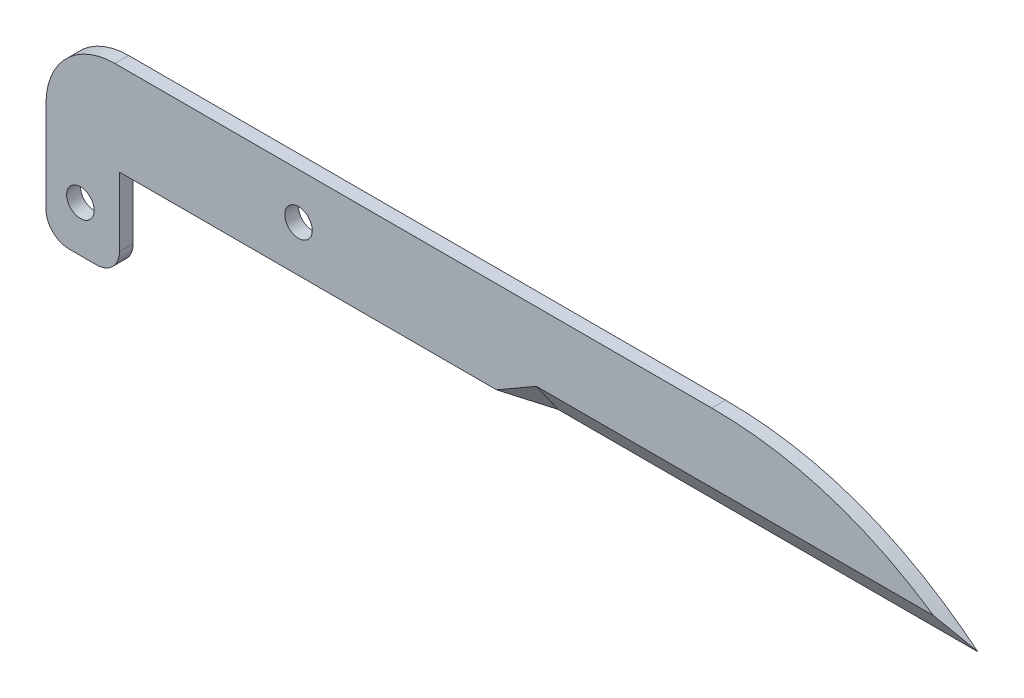
SolidWorks part; units mm, degrees
ref_plane "前视基准面" through (0, 0, 0) normal (0, 0, 1) x (1, 0, 0)
ref_plane "上视基准面" through (0, 0, 0) normal (0, 1, 0) x (1, 0, 0)
ref_plane "右视基准面" through (0, 0, 0) normal (1, 0, 0) x (0, 0, -1)
sketch "草图1" plane through (0, 0, 0) normal (0, 0, 1) x (1, 0, 0)
  line L1 (100, -10) -> (-100, -10)
  line L2 (100, -10) -> (100, 10)
  line L3 (100, 10) -> (-100, 10)
  line L4 (-100, -10) -> (-100, 10)
  line L5 (100, -10) -> (-100, 10) construction
  line L6 (100, 10) -> (-100, -10) construction
  point P0 (0, 0)
  dimension "D1" = 200
  dimension "D2" = 20
extrude "凸台-拉伸1" add sketch "草图1" along normal blind 3
sketch "草图2" plane through (0, 0, 3) normal (0, 0, 1) x (1, 0, 0)
  line L0 (21.8012, -4.3413) -> (12, -10) construction
  line L1 (-100, -10) -> (100, -10) construction
  dimension "D1" = 12
  dimension "D2" = 30
ref_plane "基准面1" through (7.3301, -12.6962, 0) normal (-0.5, 0.866, 0) x (-0.866, -0.5, 0)
sketch "草图3" plane through (100, 0, 0) normal (1, 0, 0) x (0, 0, -1)
  line L0 (-3, -5) -> (0, -10)
  line L1 (-3, -10) -> (-3, 10) construction
  line L2 (0, -10) -> (-3, -10)
  line L3 (-3, -10) -> (-3, -5)
  dimension "D1" = 5
extrude "切除-拉伸1" cut sketch "草图3" against normal up to surface (88 mm away) up to plane "基准面1"
chamfer "倒角1" distance 4 angle 60 1 edges at (16.3301, -7.5, 3)
sketch "草图4" plane through (0, 0, 3) normal (0, 0, 1) x (1, 0, 0)
  line L0 (100, 10) -> (-100, 10) construction
  line L1 (45, 10) -> (45, 14.1183)
  line L2 (45, 14.1183) -> (100, 14.1183)
  line L3 (100, 14.1183) -> (100, -10)
  spline S0 degree 2 poles (100, -10) (75.2925, 10) (45, 10) knots 0 0 0 1 1 1
  dimension "D1" = 55
extrude "切除-拉伸2" cut sketch "草图4" against normal through all
sketch "草图5" plane through (0, 0, 3) normal (0, 0, 1) x (1, 0, 0)
  line L0 (-100, 10) -> (-100, -10) construction
  circle A0 centre (-45, 0) radius 3
  dimension "D2" = 6
  dimension "D1" = 55
extrude "切除-拉伸3" cut sketch "草图5" against normal blind 4
sketch "草图8" plane through (0, 0, 3) normal (0, 0, 1) x (1, 0, 0)
  line L0 (-100, -30) -> (-100, -10)
  line L1 (-100, -10) -> (-84, -10)
  line L2 (-84, -10) -> (-84, -30)
  line L4 (-84, -30) -> (-100, -30)
  dimension "D1" = 16
  dimension "D2" = 20
extrude "凸台-拉伸2" add sketch "草图8" against normal blind 3
sketch "草图7" plane through (0, 0, 3) normal (0, 0, 1) x (1, 0, 0)
  line L0 (-100, 10) -> (-100, -30) construction
  line L2 (-100, -30) -> (-84, -30) construction
  circle A0 centre (-92.5, -20) radius 3
  dimension "D1" = 7.5
  dimension "D2" = 6
  dimension "D3" = 10
extrude "切除-拉伸5" cut sketch "草图7" against normal blind 10
fillet "圆角1" radius 15 1 edges at (-100, 10, 1.5)
fillet "圆角2" radius 5 2 edges at (-100, -30, 1.5) (-84, -30, 1.5)
